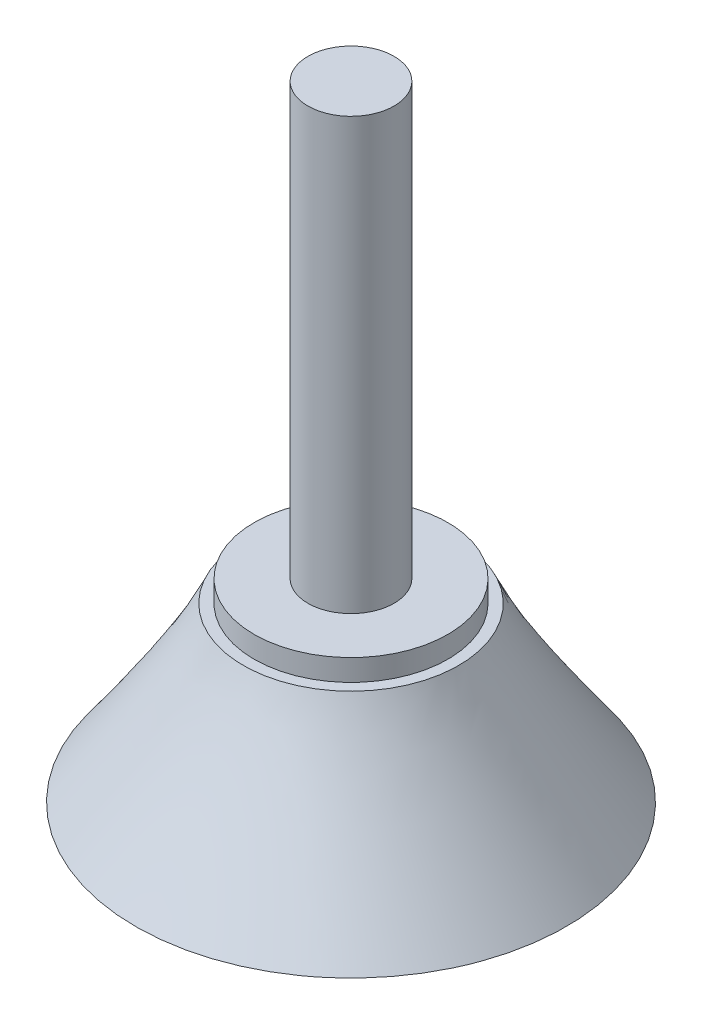
SolidWorks part; units mm, degrees
material "AISI 1020 Steel, Cold Rolled"
ref_plane "Front Plane" through (0, 0, 0) normal (0, 0, 1) x (1, 0, 0)
ref_plane "Top Plane" through (0, 0, 0) normal (0, 1, 0) x (1, 0, 0)
ref_plane "Right Plane" through (0, 0, 0) normal (1, 0, 0) x (0, 0, -1)
sketch "Sketch1" plane through (0, 0, 0) normal (0, 1, 0) x (1, 0, 0)
  circle A0 centre (0, 0) radius 50
  dimension "D1" = 100
ref_plane "Plane1" through (0, 40, 0) normal (0, 1, 0) x (1, 0, 0)
sketch "Sketch2" plane through (0, 40, 0) normal (0, 1, 0) x (1, 0, 0)
  circle A0 centre (0, 0) radius 25
  dimension "D1" = 50
loft "Loft1" add profiles "Sketch1", "Sketch2" connector at (-39.8138, 0, -30.2466) connector at (-24.8846, 40, -2.3996)
sketch "Sketch8" plane through (0, 40, 0) normal (0, 1, 0) x (1, 0, 0)
  circle A0 centre (0, 0) radius 22.5
extrude "Boss-Extrude1" add sketch "Sketch8" along normal blind 5
sketch "Sketch9" plane through (0, 45, 0) normal (0, 1, 0) x (1, 0, 0)
  circle A0 centre (0, 0) radius 10
  dimension "D1" = 20
extrude "Boss-Extrude2" add sketch "Sketch9" along normal blind 100
